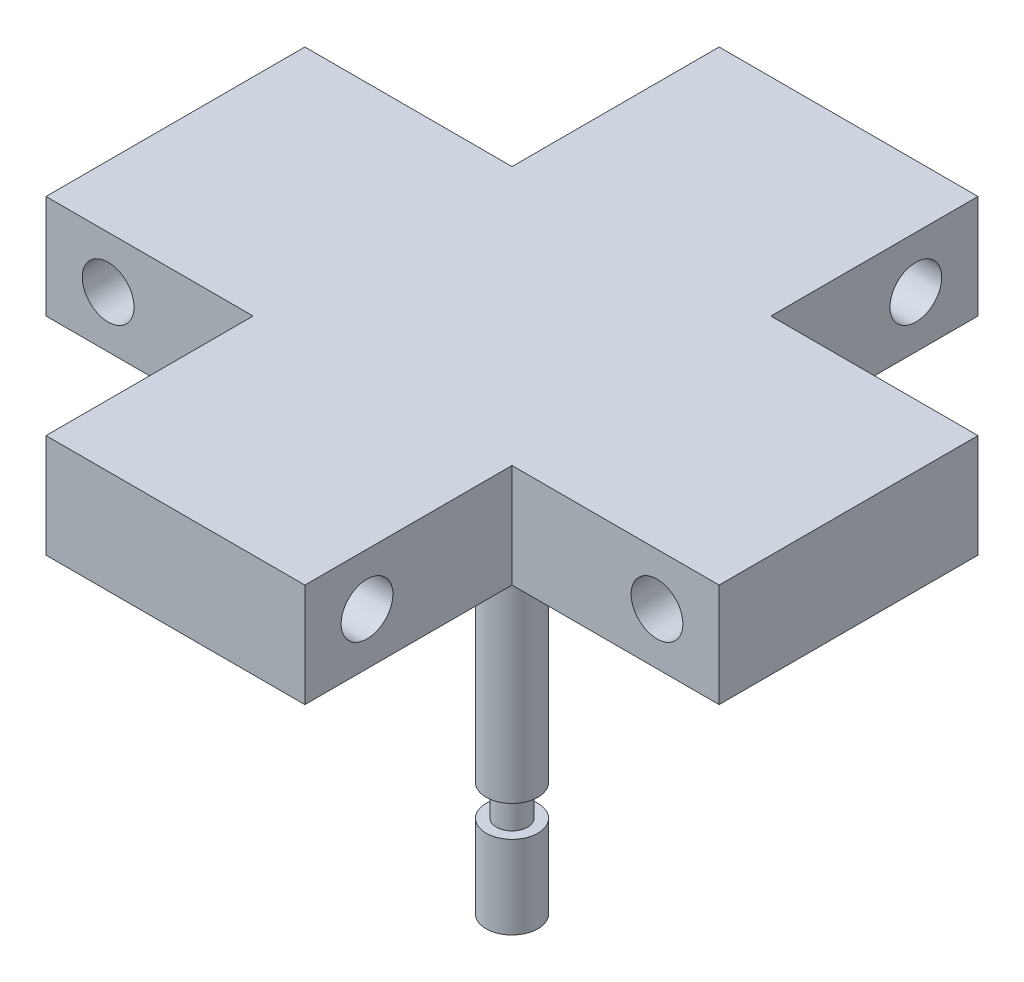
SolidWorks part; units mm, degrees
ref_plane "Front Plane" through (0, 0, 0) normal (0, 0, 1) x (1, 0, 0)
ref_plane "Top Plane" through (0, 0, 0) normal (0, 1, 0) x (1, 0, 0)
ref_plane "Right Plane" through (0, 0, 0) normal (1, 0, 0) x (0, 0, -1)
sketch "Sketch1" plane through (0, 0, 0) normal (0, 1, 0) x (1, 0, 0)
  line L1 (12.5, -12.5) -> (-12.5, -12.5)
  line L2 (12.5, -12.5) -> (12.5, 12.5)
  line L3 (12.5, 12.5) -> (-12.5, 12.5)
  line L4 (-12.5, -12.5) -> (-12.5, 12.5)
  line L5 (12.5, -12.5) -> (-12.5, 12.5) construction
  line L6 (12.5, 12.5) -> (-12.5, -12.5) construction
  line L7 (-12.5, 12.5) -> (12.5, 12.5)
  line L8 (-12.5, 12.5) -> (-12.5, 32.5)
  line L9 (-12.5, 32.5) -> (12.5, 32.5)
  line L10 (12.5, 12.5) -> (12.5, 32.5)
  line L11 (12.5, 12.5) -> (32.5, 12.5)
  line L12 (12.5, 12.5) -> (12.5, -12.5)
  line L13 (12.5, -12.5) -> (32.5, -12.5)
  line L14 (32.5, 12.5) -> (32.5, -12.5)
  line L15 (12.5, -12.5) -> (-12.5, -12.5)
  line L16 (12.5, -12.5) -> (12.5, -32.5)
  line L17 (12.5, -32.5) -> (-12.5, -32.5)
  line L18 (-12.5, -12.5) -> (-12.5, -32.5)
  line L19 (-12.5, 12.5) -> (-32.5, 12.5)
  line L20 (-12.5, 12.5) -> (-12.5, -12.5)
  line L21 (-12.5, -12.5) -> (-32.5, -12.5)
  line L22 (-32.5, 12.5) -> (-32.5, -12.5)
  point P0 (0, 0)
  dimension "D1" = 25
  dimension "D2" = 65
  dimension "D3" = 65
extrude "Boss-Extrude1" add sketch "Sketch1" along normal blind 10 contours L19 L22 L21 L4 | L1 L18 L17 L16 | L4 L1 L2 L3 | L3 L10 L9 L8 | L14 L11 L2 L13 region at (0, 0, 22.5) region at (0, 0, 0) region at (22.5, 0, 0) region at (-22.5, 0, 0) region at (0, 0, -22.5)
sketch "Sketch2" plane through (12.5, 0, 0) normal (1, 0, 0) x (0, 0, -1)
  circle A0 centre (-26.5, 5) radius 2.5
  circle A1 centre (26.5, 5) radius 2.5
extrude "Cut-Extrude1" cut sketch "Sketch2" against normal through all
sketch "Sketch3" plane through (0, 0, 12.5) normal (0, 0, 1) x (1, 0, 0)
  circle A0 centre (26.5, 5) radius 2.5 construction
  circle A1 centre (-26.5, 5) radius 2.5 construction
  circle A2 centre (26.5, 5) radius 2.5
  circle A3 centre (-26.5, 5) radius 2.5
extrude "Cut-Extrude2" cut sketch "Sketch3" against normal through all
sketch "Sketch4" plane through (0, 0, 0) normal (0, 1, 0) x (1, 0, 0)
  circle A0 centre (0, 0) radius 2.5
  dimension "D1" = 5
extrude "Boss-Extrude2" add sketch "Sketch4" against normal blind 40
sketch "Sketch5" plane through (0, 0, 0) normal (1, 0, 0) x (0, 0, -1)
  line L0 (0, 0) -> (0, -40) construction
  line L1 (-2.5, -40) -> (2.5, -40) construction
  line L2 (2.5, -29) -> (1.5, -29)
  line L4 (2.5, -40) -> (2.5, 0) construction
  line L5 (1.5, -29) -> (1.5, -32)
  line L6 (1.5, -32) -> (2.5, -32)
  line L7 (2.5, -29) -> (2.5, -32)
  dimension "D1" = 1
  dimension "D2" = 8
  dimension "D3" = 3
revolve "Cut-Revolve1" cut sketch "Sketch5" angle 360 about L0
